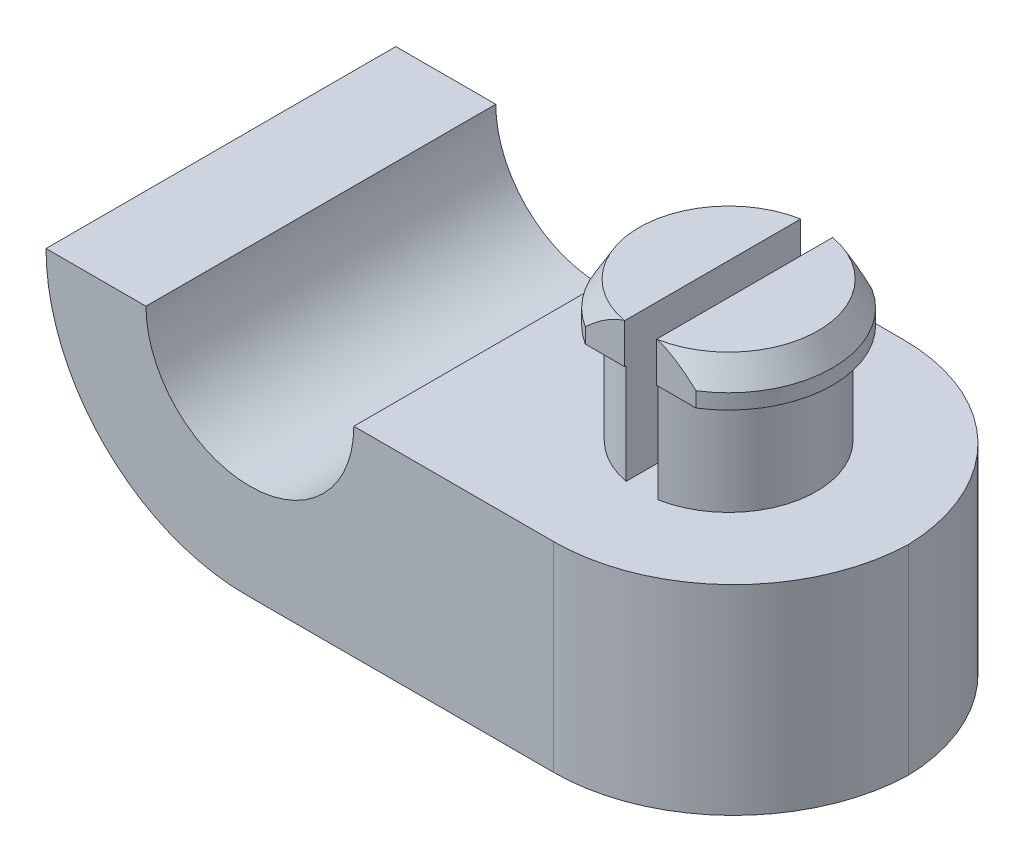
SolidWorks part; units mm, degrees
ref_plane "Front Plane" through (0, 0, 0) normal (0, 0, 1) x (1, 0, 0)
ref_plane "Top Plane" through (0, 0, 0) normal (0, 1, 0) x (1, 0, 0)
ref_plane "Right Plane" through (0, 0, 0) normal (1, 0, 0) x (0, 0, -1)
sketch "Sketch1" plane through (0, 0, 0) normal (0, 0, 1) x (1, 0, 0)
  line L0 (3.302, 0) -> (15.367, 0)
  line L1 (-6.477, 0) -> (-3.302, 0)
  line L2 (-6.477, 0) -> (-6.477, -6.35)
  line L3 (-6.477, -6.35) -> (15.367, -6.35)
  line L4 (15.367, 0) -> (15.367, -6.35)
  arc A0 (-3.302, 0) -> (3.302, 0) centre (0, 0) ccw
  dimension "D1" = 3.302
  dimension "D2" = 3.175
  dimension "D3" = 6.35
  dimension "D4" = 21.844
extrude "Boss-Extrude1" add sketch "Sketch1" along normal blind 11.1125 contours L2 L3 L4 L0 A0 L1
fillet "Fillet1" radius 6.35 1 edges at (-6.477, -6.35, 5.5562)
fillet "Fillet2" radius 5.715 2 edges at (15.367, -3.175, 0) (15.367, -3.175, 11.1125)
sketch "Sketch2" plane through (0, 0, 0) normal (0, 1, 0) x (1, 0, 0)
  circle A0 centre (9.652, -5.5562) radius 2.794
  dimension "D1" = 5.588
extrude "Boss-Extrude2" add sketch "Sketch2" along normal blind 3.175
sketch "Sketch3" plane through (0, 3.175, 0) normal (0, 1, 0) x (1, 0, 0)
  line L4 (7.8922, -8.3503) -> (11.4118, -8.3503)
  line L8 (7.8922, -2.7622) -> (11.4118, -2.7622)
  arc A0 (11.4118, -8.3503) -> (11.4118, -2.7622) centre (9.652, -5.5562) ccw
  circle A1 centre (9.652, -5.5562) radius 2.794 construction
  circle A2 centre (9.652, -5.5562) radius 2.794 construction
  arc A3 (7.8922, -2.7622) -> (7.8922, -8.3503) centre (9.652, -5.5562) ccw
  dimension "D1" = 6.604
extrude "Boss-Extrude3" add sketch "Sketch3" along normal blind 1.27
sketch "Sketch4" plane through (0, 0, 0) normal (0, 0, 1) x (1, 0, 0)
  line L0 (12.954, 4.445) -> (11.4118, 4.445) construction
  line L1 (9.144, 4.445) -> (10.16, 4.445)
  line L2 (9.144, 4.445) -> (9.144, 0)
  line L3 (9.144, 0) -> (10.16, 0)
  line L4 (10.16, 4.445) -> (10.16, 0)
  line L6 (9.652, 4.445) -> (9.652, 0) construction
  line L7 (9.652, -6.35) -> (9.652, 0) construction
  line L8 (12.446, 0) -> (6.858, 0) construction
  dimension "D1" = 1.016
extrude "Cut-Extrude2" cut sketch "Sketch4" along normal through all
chamfer "Chamfer1" distance 0.7937 angle 30 2 edges at (6.35, 4.445, 5.5562) (12.954, 4.445, 5.5562) first distance on face at (7.1211, 3.81, 5.5562) first distance on face at (12.1829, 3.81, 5.5562)
